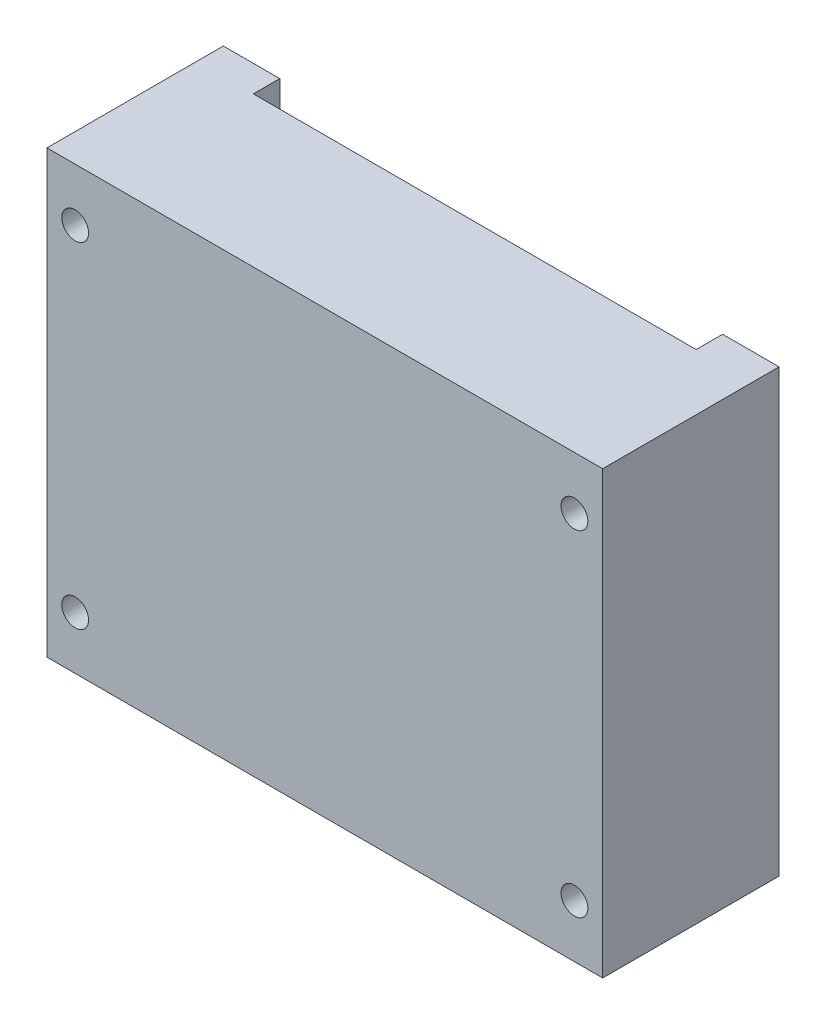
SolidWorks part; units mm, degrees
ref_plane "Front Plane" through (0, 0, 0) normal (0, 0, 1) x (1, 0, 0)
ref_plane "Top Plane" through (0, 0, 0) normal (0, 1, 0) x (1, 0, 0)
ref_plane "Right Plane" through (0, 0, 0) normal (1, 0, 0) x (0, 0, -1)
sketch "Sketch1" plane through (0, 0, 0) normal (0, 0, 1) x (1, 0, 0)
  line L1 (-40.005, 31.75) -> (40.005, 31.75)
  line L2 (-40.005, 31.75) -> (-40.005, -31.75)
  line L3 (-40.005, -31.75) -> (40.005, -31.75)
  line L4 (40.005, 31.75) -> (40.005, -31.75)
  dimension "D1" = 63.5
  dimension "D2" = 80.01
  dimension "D3" = 31.75
  dimension "D4" = 40.005
extrude "Boss-Extrude1" add sketch "Sketch1" along normal blind 25.4
sketch "Sketch2" plane through (0, 0, 0) normal (0, 0, 1) x (1, 0, 0)
  line L1 (31.877, 28.575) -> (-31.877, 28.575)
  line L2 (31.877, 28.575) -> (31.877, -28.575)
  line L3 (31.877, -28.575) -> (-31.877, -28.575)
  line L4 (-31.877, 28.575) -> (-31.877, -28.575)
  line L5 (40.005, -31.75) -> (40.005, 31.75) construction
  line L6 (-40.005, 31.75) -> (-40.005, -31.75) construction
  dimension "D1" = 8.128
  dimension "D2" = 28.575
  dimension "D3" = 57.15
  dimension "D4" = 8.128
extrude "Cut-Extrude1" cut sketch "Sketch2" along normal blind 22.86
sketch "Sketch3" plane through (0, 0, 0) normal (0, 1, 0) x (1, 0, 0)
  line L5 (-40.005, -25.4) -> (-40.005, 0) construction
  line L6 (40.005, -25.4) -> (40.005, 0) construction
  line L7 (-40.005, -12.7) -> (40.005, -12.7) construction
  line L8 (31.877, -3.81) -> (31.877, 0)
  line L9 (-31.877, 0) -> (31.877, 0)
  line L10 (-31.877, -3.81) -> (-31.877, 0)
  line L11 (-31.877, -3.81) -> (31.877, -3.81)
  line L12 (-55, 0) -> (55, 0) construction
  dimension "D1" = 3.81
  dimension "D2" = 8.128
  dimension "D3" = 8.128
extrude "Cut-Extrude2" cut sketch "Sketch3" against normal through all both and the other way through all
sketch "Sketch6" plane through (0, 0, 0) normal (0, 0, 1) x (1, 0, 0)
  line L0 (35.941, 31.75) -> (35.941, -31.75) construction
  line L1 (40.005, 31.75) -> (31.877, 31.75) construction
  line L2 (31.877, -31.75) -> (40.005, -31.75) construction
  line L3 (55, 0) -> (-55, 0) construction
  line L4 (0, -55) -> (0, 55) construction
  point P6 (35.941, 24.13)
  point P10 (35.941, -24.13)
  point P14 (-35.941, -24.13)
  point P15 (-35.941, 24.13)
  dimension "D1" = 7.62
hole_wizard "#8 Clearance Hole1" positions "Sketch7" profile "Sketch8" hole size "#8" standard "ANSI Inch" end condition through all
sketch "Sketch7" plane through (0, 0, 0) normal (0, 0, -1) x (-1, 0, 0)
  point P0 (-35.941, 24.13)
  point P3 (-35.941, -24.13)
  point P6 (35.941, -24.13)
  point P9 (35.941, 24.13)
sketch "Sketch8" plane through (35.941, 24.13, 0) normal (1, 0, 0) x (0, 1, 0)
  line L0 (0, 0) -> (0, 25.4)
  line L1 (0, 25.4) -> (1.9304, 25.4)
  line L2 (1.9304, 25.4) -> (1.9304, 0)
  line L5 (1.9304, 0) -> (0, 0)
  line L11 (0, -6.35) -> (0, 107.95) construction
  dimension "Thru Hole Dia." = 3.8608
  dimension "Thru Hole Depth" = 25.4
sketch "Sketch11" plane through (0, 0, 0) normal (0, 0, 1) x (1, 0, 0)
  line L0 (0, -13.97) -> (0, 13.97) construction
  line L1 (-40.005, -31.75) -> (40.005, -31.75) construction
  point P0 (0, -21.59)
  dimension "D1" = 10.16
sketch "Sketch13" plane through (0, 0, 0) normal (0, 1, 0) x (1, 0, 0)
  line L0 (-31.877, -3.81) -> (31.877, -3.81) construction
  line L1 (0, -13.97) -> (0, 13.97) construction
  line L2 (-5.08, -3.81) -> (-5.08, -20.32)
  line L3 (-5.08, -20.32) -> (5.08, -20.32)
  line L4 (5.08, -20.32) -> (5.08, -3.81)
  line L6 (-5.08, -3.81) -> (5.08, -3.81)
  point P0 (-5.08, -3.81)
  point P1 (-5.08, -20.32)
  point P4 (5.08, -20.32)
  point P5 (5.08, -3.81)
  point P10 (0, 0)
  point P13 (0, 0)
  point P14 (0, 0)
  point P15 (0, 0)
  point P16 (0, 0)
  dimension "D1" = 5.08
  dimension "D2" = 5.08
  dimension "D3" = 5.08
  dimension "D4" = 5.08
  dimension "D5" = 16.51
  dimension "D6" = 16.51
extrude "Cut-Extrude3" cut sketch "Sketch13" against normal blind 50.8
